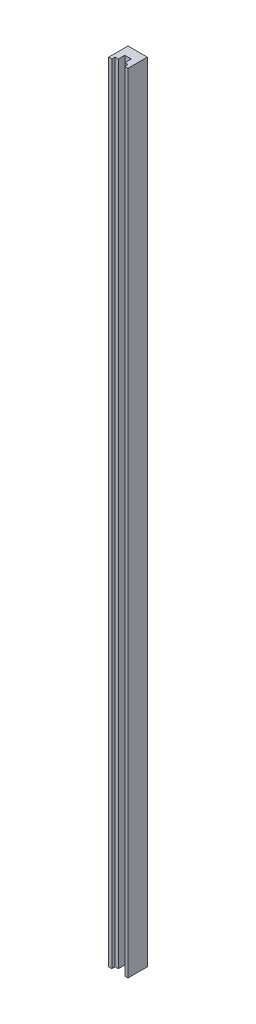
SolidWorks part; units mm, degrees
ref_plane "Front" through (0, 0, 0) normal (0, 0, 1) x (1, 0, 0)
ref_plane "Top" through (0, 0, 0) normal (0, 1, 0) x (1, 0, 0)
ref_plane "Right" through (0, 0, 0) normal (1, 0, 0) x (0, 0, -1)
sketch "Sketch1" plane through (0, 0, 0) normal (0, 1, 0) x (1, 0, 0)
  line L1 (15, -15) -> (-15, -15)
  line L2 (15, -15) -> (15, 15)
  line L3 (15, 15) -> (-15, 15)
  line L4 (-15, -15) -> (-15, 15)
  line L5 (15, -15) -> (-15, 15) construction
  line L6 (15, 15) -> (-15, -15) construction
  point P0 (0, 0)
  dimension "D1" = 30
  dimension "D2" = 30
extrude "Boss-Extrude1" add sketch "Sketch1" along normal blind 1225
sketch "Sketch2" plane through (0, 1225, 0) normal (0, 1, 0) x (1, 0, 0)
  line L0 (-15, -15) -> (15, -15) construction
  line L1 (-10, -15) -> (10, -15)
  line L2 (-10, -15) -> (-10, -10)
  line L3 (-10, -10) -> (10, -10)
  line L4 (10, -15) -> (10, -10)
  line L5 (-15, 15) -> (-15, -15) construction
  dimension "D1" = 20
  dimension "D2" = 5
  dimension "D3" = 5
extrude "Cut-Extrude1" cut sketch "Sketch2" against normal up to next
sketch "Sketch3" plane through (0, 1225, 0) normal (0, 1, 0) x (1, 0, 0)
  line L0 (10, -10) -> (-10, -10) construction
  line L1 (-5, -10) -> (5, -10)
  line L2 (-5, -10) -> (-5, 0)
  line L3 (-5, 0) -> (5, 0)
  line L4 (5, -10) -> (5, 0)
  line L5 (-10, -10) -> (-10, -15) construction
  dimension "D1" = 10
  dimension "D2" = 10
  dimension "D3" = 5
extrude "Cut-Extrude2" cut sketch "Sketch3" against normal up to next
sketch "Sketch4" plane through (-15, 0, 0) normal (-1, 0, 0) x (0, 0, 1)
  line L0 (-15, 1200) -> (15, 1200) construction
  line L1 (-15, 1225) -> (-15, 0) construction
  line L2 (15, 1225) -> (15, 0) construction
  line L3 (-15, 1000) -> (15, 1000) construction
  line L4 (-15, 800) -> (15, 800) construction
  line L5 (-15, 0) -> (15, 0) construction
  line L6 (-15, 700) -> (15, 700) construction
  dimension "D1" = 1200
  dimension "D2" = 1000
  dimension "D3" = 800
  dimension "D4" = 700
sketch "Sketch5" plane through (-15, 0, 0) normal (-1, 0, 0) x (0, 0, 1)
  line L0 (-15, 200) -> (15, 200) construction
  line L1 (-15, 1225) -> (-15, 0) construction
  line L2 (15, 1225) -> (15, 0) construction
  line L3 (-15, 0) -> (15, 0) construction
  dimension "D1" = 200
sketch "Sketch6" plane through (0, 0, -15) normal (0, 0, -1) x (-1, 0, 0)
  line L1 (-15, 1225) -> (-15, 0) construction
  line L2 (-15, 1225) -> (15, 1225) construction
  circle A0 centre (0, 1200) radius 4
  circle A1 centre (0, 1000) radius 4
  circle A2 centre (0, 800) radius 4
  circle A3 centre (0, 700) radius 4
  circle A4 centre (0, 650) radius 4
  circle A5 centre (0, 600) radius 4
  circle A6 centre (0, 550) radius 4
  circle A7 centre (0, 500) radius 4
  circle A8 centre (0, 450) radius 4
  circle A9 centre (0, 400) radius 4
  circle A10 centre (0, 350) radius 4
  circle A11 centre (0, 300) radius 4
  circle A12 centre (0, 250) radius 4
  circle A13 centre (0, 200) radius 4
  dimension "D1" = 8
  dimension "D2" = 25
  dimension "D3" = 15
  dimension "D4" = 200
  dimension "D5" = 200
  dimension "D6" = 100
  dimension "D7" = 50
  dimension "D8" = 50
  dimension "D9" = 50
  dimension "D10" = 50
  dimension "D11" = 50
  dimension "D12" = 50
  dimension "D13" = 50
  dimension "D14" = 50
  dimension "D15" = 50
  dimension "D16" = 50
extrude "Cut-Extrude3" cut sketch "Sketch6" against normal blind 3
